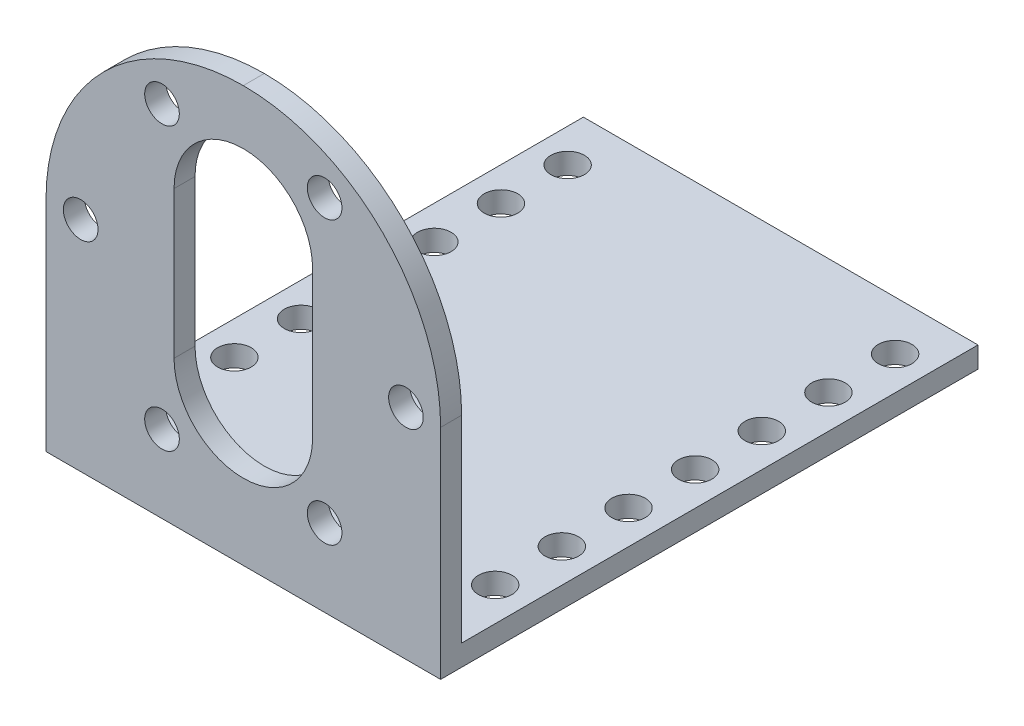
SolidWorks part; units mm, degrees
ref_plane "Front Plane" through (0, 0, 0) normal (0, 0, 1) x (1, 0, 0)
ref_plane "Top Plane" through (0, 0, 0) normal (0, 1, 0) x (1, 0, 0)
ref_plane "Right Plane" through (0, 0, 0) normal (1, 0, 0) x (0, 0, -1)
sketch "Sketch1" plane through (0, 0, 0) normal (0, 1, 0) x (1, 0, 0)
  line L1 (-18.8, -25.6) -> (18.8, -25.6)
  line L2 (-18.8, -25.6) -> (-18.8, 25.6)
  line L3 (-18.8, 25.6) -> (18.8, 25.6)
  line L4 (18.8, -25.6) -> (18.8, 25.6)
  line L5 (-18.8, -25.6) -> (18.8, 25.6) construction
  line L6 (-18.8, 25.6) -> (18.8, -25.6) construction
  point P0 (0, 0)
  dimension "D1" = 37.6
  dimension "D2" = 51.2
extrude "Boss-Extrude1" add sketch "Sketch1" along normal blind 39.6
sketch "Sketch2" plane through (0, 39.6, 0) normal (0, 1, 0) x (1, 0, 0)
  line L0 (18.8, -25.6) -> (18.8, 25.6) construction
  line L1 (-18.8, 25.6) -> (18.8, 25.6)
  line L2 (-18.8, 25.6) -> (-18.8, -23.6)
  line L3 (-18.8, -23.6) -> (18.8, -23.6)
  line L4 (18.8, 25.6) -> (18.8, -23.6)
  line L5 (-18.8, -25.6) -> (18.8, -25.6) construction
  dimension "D1" = 2
extrude "Cut-Extrude1" cut sketch "Sketch2" against normal offset from surface (37.6 mm away) 2 up to face at (0, 0, 0)
fillet "Fillet1" radius 18.8 2 edges at (18.8, 39.6, 24.6) (-18.8, 39.6, 24.6)
sketch "Sketch4" plane through (0, 0, 0) normal (0, -1, 0) x (1, 0, 0)
  line L0 (-15.6, 25.6) -> (-15.6, -25.6) construction
  line L1 (-18.8, 25.6) -> (18.8, 25.6) construction
  line L2 (18.8, -25.6) -> (-18.8, -25.6) construction
  line L3 (15.6, 25.6) -> (15.6, -25.6) construction
  line L5 (-15.6, 0) -> (15.6, 0) construction
  circle A0 centre (-15.6, 17.2) radius 1.6
  circle A1 centre (15.6, 17.2) radius 1.6
  circle A2 centre (-15.6, 10.85) radius 1.6
  circle A3 centre (15.6, 10.85) radius 1.6
  circle A4 centre (-15.6, 4.5) radius 1.6
  circle A5 centre (15.6, 4.5) radius 1.6
  circle A6 centre (-15.6, -1.85) radius 1.6
  circle A7 centre (15.6, -1.85) radius 1.6
  circle A8 centre (-15.6, -8.2) radius 1.6
  circle A9 centre (15.6, -8.2) radius 1.6
  circle A10 centre (-15.6, -14.55) radius 1.6
  circle A11 centre (15.6, -14.55) radius 1.6
  circle A12 centre (-15.6, -20.9) radius 1.6
  circle A13 centre (15.6, -20.9) radius 1.6
  point P10 (0, 0)
  dimension "D2" = 3.2
  dimension "D1" = 31.2
  dimension "D3" = 8.4
  dimension "D4" = 8.4
  dimension "D6" = 4.7
  dimension "D5" = 7
extrude "Cut-Extrude2" cut sketch "Sketch4" against normal through all
sketch "Sketch5" plane through (0, 0, 25.6) normal (0, 0, 1) x (1, 0, 0)
  line L0 (0, 39.6) -> (0, 2) construction
  line L1 (0, 27.8) -> (0, 13.8) construction
  line L2 (6.6, 27.8) -> (6.6, 13.8)
  line L3 (-6.6, 27.8) -> (-6.6, 13.8)
  line L4 (-15.494, 20.8) -> (15.494, 20.8) construction
  line L5 (-7.747, 34.2182) -> (0, 20.8) construction
  line L6 (7.747, 34.2182) -> (0, 20.8) construction
  line L7 (-7.747, 7.3818) -> (0, 20.8) construction
  line L8 (7.747, 7.3818) -> (0, 20.8) construction
  circle A0 centre (0, 20.8) radius 18.8 construction
  arc A1 (6.6, 27.8) -> (-6.6, 27.8) centre (0, 27.8) ccw
  arc A2 (-6.6, 13.8) -> (6.6, 13.8) centre (0, 13.8) ccw
  arc A3 (0, 39.6) -> (-18.8, 20.8) centre (0, 20.8) ccw construction
  circle A4 centre (0, 20.8) radius 15.494 construction
  circle A5 centre (-15.494, 20.8) radius 1.65
  circle A6 centre (15.494, 20.8) radius 1.65
  circle A7 centre (-7.747, 34.2182) radius 1.65
  circle A8 centre (7.747, 34.2182) radius 1.65
  circle A9 centre (7.747, 7.3818) radius 1.65
  circle A10 centre (-7.747, 7.3818) radius 1.65
  point P6 (0, 20.8)
  dimension "D3" = 30.988
  dimension "D4" = 3.3
  dimension "D1" = 13.2
  dimension "D2" = 14
  dimension "D5" = 60
  dimension "D6" = 60
  dimension "D7" = 60
  dimension "D8" = 60
extrude "Cut-Extrude3" cut sketch "Sketch5" against normal through all
